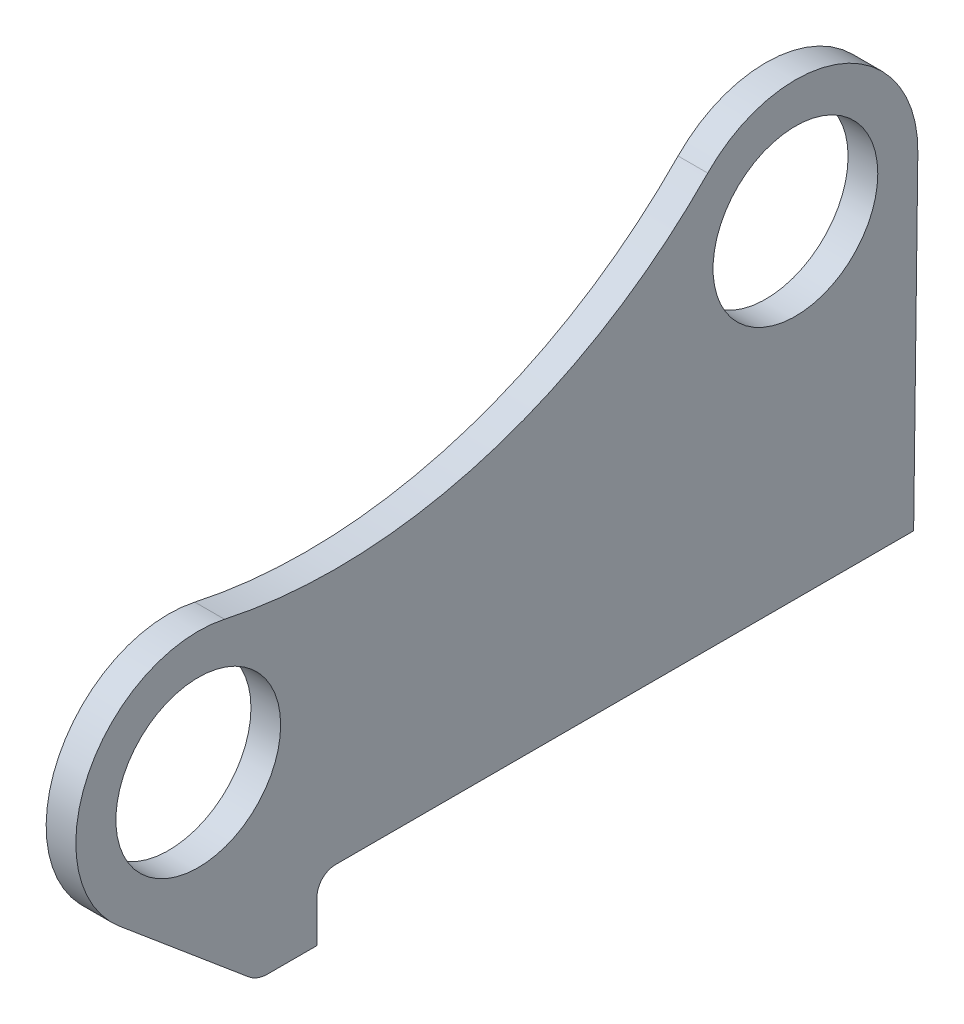
SolidWorks part; units mm, degrees
material "MS-Grade 350"
ref_plane "Front Plane" through (0, 0, 0) normal (0, 0, 1) x (1, 0, 0)
ref_plane "Top Plane" through (0, 0, 0) normal (0, 1, 0) x (1, 0, 0)
ref_plane "Right Plane" through (0, 0, 0) normal (1, 0, 0) x (0, 0, -1)
sketch "Sketch1" plane through (0, 0, 0) normal (1, 0, 0) x (0, 0, -1)
  line L0 (0, -41) -> (0, -12.5)
  line L1 (12.5, 0) -> (402, 0)
  line L3 (402, 0) -> (404.8313, 219.4513)
  line L4 (-133.0582, 36.825) -> (-45.9722, -36.3151)
  line L11 (0, -41) -> (-33.1096, -41)
  line L12 (-80, 100) -> (322.3381, 220.5156) construction
  circle A0 centre (-80, 100) radius 55.5
  circle A1 centre (322.3381, 220.5156) radius 55.5
  arc A2 (-62.3216, 180.5837) -> (-133.0582, 36.825) centre (-80, 100) ccw
  arc A4 (-45.9722, -36.3151) -> (-33.1096, -41) centre (-33.1096, -21) ccw
  arc A5 (0, -12.5) -> (12.5, 0) centre (12.5, -12.5) cw
  arc A9 (404.8313, 219.4513) -> (263.2699, 278.1108) centre (322.3381, 220.5156) ccw
  arc A10 (-62.3216, 180.5837) -> (263.2699, 278.1108) centre (12.6776, 522.4537) ccw
  point P31 (0, 0)
  dimension "D2" = 100
  dimension "D4" = 82.5
  dimension "D5" = 111
  dimension "D6" = 41
  dimension "D7" = 350
  dimension "D13" = 40.026
  dimension "D20" = 12.5
  dimension "D3" = 20
  dimension "D12" = 402
  dimension "D15" = 16.675
  dimension "D16" = 420
  dimension "D17" = 80
sheet metal parameters "Sheet-Metal1" thickness 20 parameters "D1"=92
base flange "Base-Flange1" sketch "Sketch1" thickness 20 reverse thickness direction no parameters "D1"=92
fillet "Fillet-1.0" [suppressed] radius 1
flat pattern "Flat-Pattern1" [suppressed]
sketch "Bend-Lines1" plane through (0, 0, 0) normal (0, 1, 0) x (1, 0, 0)
sketch3d "Bounding-Box1" [suppressed]
  line L0 (-159.706, -578.3518, 0) -> (414.8034, -519.7595, 0) construction
  line L1 (-191.145, -270.0857, 0) -> (383.3643, -211.4933, 0) construction
  line L2 (-159.706, -578.3518, 0) -> (-191.145, -270.0857, 0) construction
  line L3 (414.8034, -519.7595, 0) -> (383.3643, -211.4933, 0) construction
